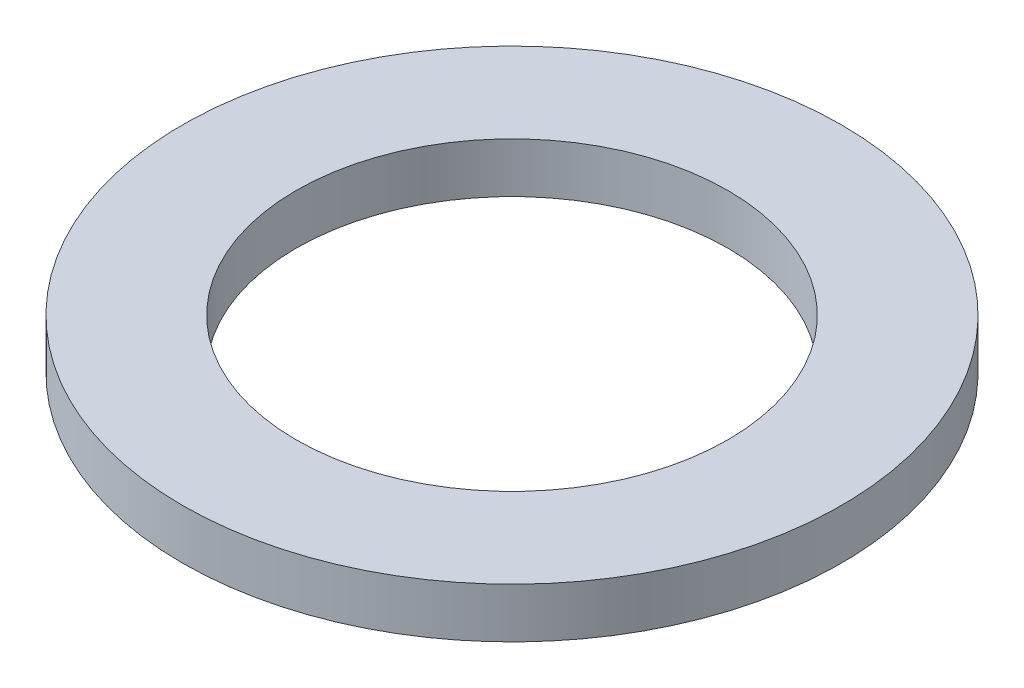
SolidWorks part; units mm, degrees
ref_plane "Front Plane" through (0, 0, 0) normal (0, 0, 1) x (1, 0, 0)
ref_plane "Top Plane" through (0, 0, 0) normal (0, 1, 0) x (1, 0, 0)
ref_plane "Right Plane" through (0, 0, 0) normal (1, 0, 0) x (0, 0, -1)
sketch "Sketch1" plane through (0, 0, 0) normal (0, 1, 0) x (1, 0, 0)
  circle A0 centre (0, 0) radius 72.5
  dimension "FLANGE_OD" = 145
extrude "Boss-Extrude1" add sketch "Sketch1" along normal blind 11
sketch "Sketch2" plane through (0, 0, 0) normal (0, 1, 0) x (1, 0, 0)
  circle A0 centre (0, 0) radius 47.5
  dimension "BORE_D" = 95
extrude "Cut-Extrude1" cut sketch "Sketch2" along normal through all
sketch "Sketch3" plane through (0, 11, 0) normal (0, 1, 0) x (1, 0, 0)
  circle A0 centre (0, 0) radius 30.9309 construction
  circle A1 centre (-30.9309, 0) radius 2.7729
  dimension "BOLT_D" = 5.5458
  dimension "BOLT_PCD" = 61.8617
extrude "Cut-Extrude2" cut sketch "Sketch3" against normal blind 8.0101 rebuild error yes
pattern_circular "CirPattern1" count 5 over 360 rebuild error yes
